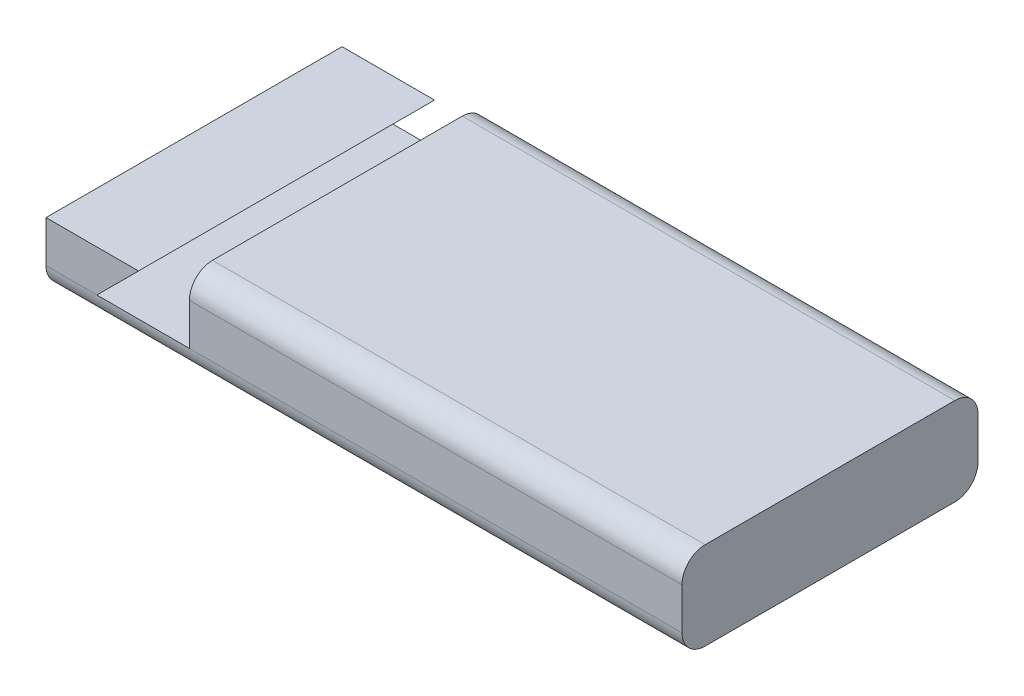
SolidWorks part; units mm, degrees
material "7079 Alloy"
ref_plane "Front Plane" through (0, 0, 0) normal (0, 0, 1) x (1, 0, 0)
ref_plane "Top Plane" through (0, 0, 0) normal (0, 1, 0) x (1, 0, 0)
ref_plane "Right Plane" through (0, 0, 0) normal (1, 0, 0) x (0, 0, -1)
sketch "Sketch1" plane through (0, 0, 0) normal (0, 1, 0) x (1, 0, 0)
  line L1 (0, 0) -> (55, 0)
  line L2 (0, 0) -> (0, 25.6)
  line L3 (0, 25.6) -> (55, 25.6)
  line L4 (55, 0) -> (55, 25.6)
  dimension "D1" = 55
  dimension "D2" = 25.6
extrude "Boss-Extrude1" add sketch "Sketch1" along normal blind 7.6
sketch "Sketch2" plane through (0, 0, -25.6) normal (0, 0, -1) x (-1, 0, 0)
  line L1 (-8, 5.6) -> (-4.4, 2)
  line L2 (-12.4, 7.6) -> (0, 7.6)
  line L3 (0, 5.6) -> (-8, 5.6)
  line L4 (-12.4, 2) -> (-4.4, 2)
  line L5 (-55, 0) -> (0, 0) construction
  line L8 (-12.4, 7.6) -> (-12.4, 2)
  line L11 (0, 7.6) -> (0, 5.6)
  line L12 (0, 5.6) -> (-8, 5.6)
  dimension "D1" = 8
  dimension "D2" = 8
  dimension "D3" = 45
  dimension "D4" = 2
  dimension "D5" = 2
extrude "Cut-Extrude1" cut sketch "Sketch2" against normal blind 25.6
fillet "Fillet1" radius 2 4 edges at (27.5, 0, -25.6) (27.5, 0, 0) (33.7, 7.6, -25.6) (33.7, 7.6, 0)
ref_plane "Plane1" through (0, 0, -12.8) normal (0, 0, -1) x (-1, 0, 0)
